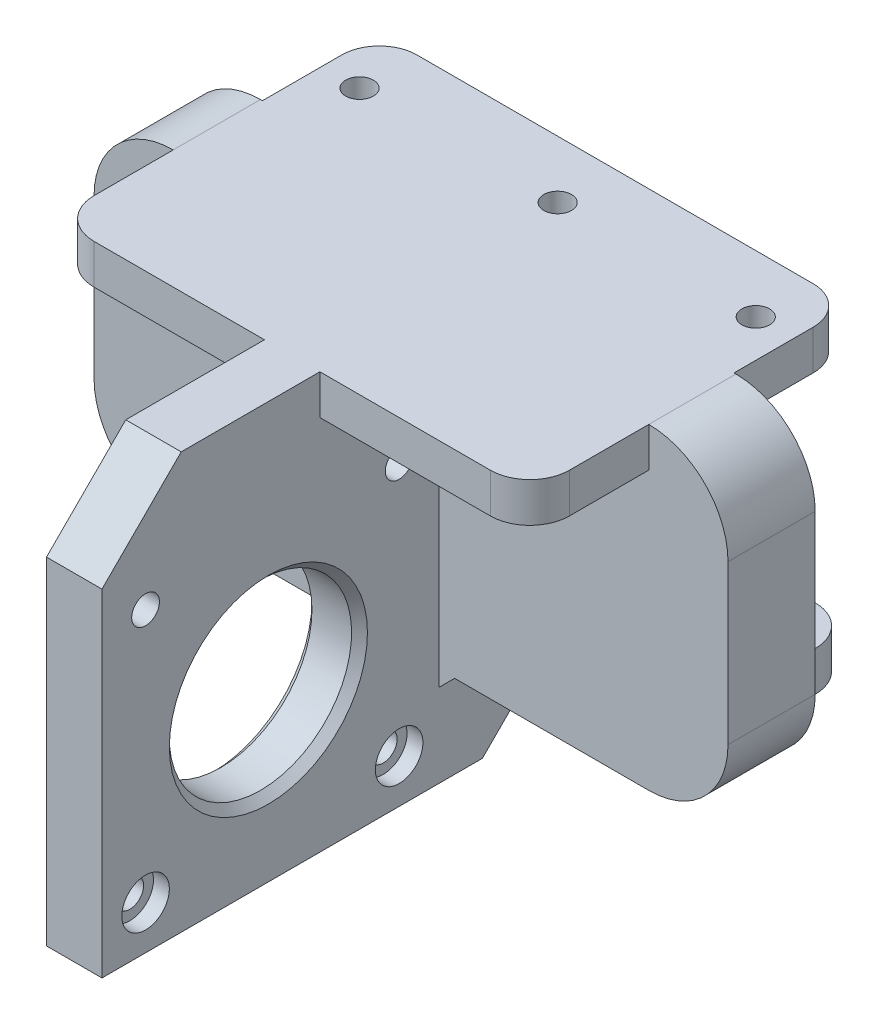
SolidWorks part; units mm, degrees
ref_plane "Front Plane" through (0, 0, 0) normal (0, 0, 1) x (1, 0, 0)
ref_plane "Top Plane" through (0, 0, 0) normal (0, 1, 0) x (1, 0, 0)
ref_plane "Right Plane" through (0, 0, 0) normal (1, 0, 0) x (0, 0, -1)
sketch "Sketch1" plane through (0, 0, 0) normal (0, 0, 1) x (1, 0, 0)
  line L0 (60, 35) -> (0, 35)
  line L1 (0, 35) -> (0, 40)
  line L2 (-10, 30) -> (-10, 10)
  line L3 (0, 0) -> (60, 0)
  line L4 (70, 10) -> (70, 30)
  line L5 (60, 40) -> (60, 35)
  arc A0 (0, 40) -> (-10, 30) centre (0, 30) ccw
  arc A1 (-10, 10) -> (0, 0) centre (0, 10) ccw
  arc A2 (60, 0) -> (70, 10) centre (60, 10) ccw
  arc A3 (70, 30) -> (60, 40) centre (60, 30) ccw
extrude "Boss-Extrude1" add sketch "Sketch1" along normal blind 11
sketch "Sketch2" plane through (0, 0, 11) normal (0, 0, 1) x (1, 0, 0)
  line L1 (0, 35) -> (60, 35)
  line L2 (0, 35) -> (0, 40)
  line L3 (0, 40) -> (60, 40)
  line L4 (60, 35) -> (60, 40)
extrude "Boss-Extrude2" add sketch "Sketch2" against normal blind 26
fillet "Fillet1" radius 5 2 edges at (60, 37.5, -15) (0, 37.5, -15)
sketch "Sketch4" plane through (0, 35, 0) normal (0, -1, 0) x (-1, 0, 0)
  line L0 (-55, 15) -> (-55, 7.5) construction
  line L1 (-30, 15) -> (-30, 7.5) construction
  line L2 (-5, 15) -> (-55, 15) construction
  line L3 (-5, 15) -> (-5, 7.5) construction
  arc A0 (0, 10) -> (-5, 15) centre (-5, 10) ccw construction
  circle A1 centre (-55, 7.5) radius 1.75
  circle A2 centre (-30, 7.5) radius 1.75
  circle A3 centre (-5, 7.5) radius 1.75
  dimension "D2" = 3.5
  dimension "D1" = 7.5
extrude "Cut-Extrude2" cut sketch "Sketch4" against normal blind 25
sketch "Sketch5" plane through (0, 35, 0) normal (0, -1, 0) x (1, 0, 0)
  line L0 (5, -14.75) -> (55, -14.75)
  line L1 (59.75, -10) -> (59.75, -0.25)
  line L3 (0.25, -0.25) -> (0.25, -10)
  line L4 (5, -15) -> (55, -15)
  line L5 (60, -10) -> (60, 0)
  line L6 (60, 0) -> (0, 0)
  line L7 (0, 0) -> (0, -10)
  line L8 (5, -15) -> (55, -15)
  line L9 (60, -10) -> (60, 0)
  line L10 (60, 0) -> (59.75, 0)
  line L11 (0, 0) -> (0, -10)
  line L12 (59.75, -0.25) -> (59.75, 0)
  line L13 (0.25, -0.25) -> (0.25, 0)
  line L14 (0.25, 0) -> (0, 0)
  line L16 (60, 0) -> (0, 0) construction
  line L17 (59.75, -0.25) -> (0.25, -0.25) construction
  arc A0 (55, -14.75) -> (59.75, -10) centre (55, -10) ccw
  arc A1 (0.25, -10) -> (5, -14.75) centre (5, -10) ccw
  arc A2 (55, -15) -> (60, -10) centre (55, -10) ccw
  arc A3 (0, -10) -> (5, -15) centre (5, -10) ccw
  arc A4 (55, -15) -> (60, -10) centre (55, -10) ccw
  arc A5 (0, -10) -> (5, -15) centre (5, -10) ccw
  dimension "D1" = 0
  dimension "D2" = 0.25
extrude "Cut-Extrude3" cut sketch "Sketch5" against normal blind 25
sketch "Sketch6" plane through (0, 0, 11) normal (0, 0, 1) x (1, 0, 0)
  line L1 (60, 40) -> (0, 40)
  line L2 (60, 40) -> (60, 35)
  line L3 (60, 35) -> (0, 35)
  line L4 (0, 40) -> (0, 35)
  dimension "D1" = 5
extrude "Boss-Extrude3" add sketch "Sketch6" along normal blind 15
fillet "Fillet2" radius 5 2 edges at (0, 37.5, 26) (60, 37.5, 26)
sketch "Sketch7" plane through (0, 0, 11) normal (0, 0, 1) x (1, 0, 0)
  line L0 (0, 35) -> (60, 35) construction
  line L1 (33.5, 35) -> (26.5, 35)
  line L2 (33.5, 35) -> (33.5, -10)
  line L3 (33.5, -10) -> (26.5, -10)
  line L4 (26.5, 35) -> (26.5, -10)
  line L5 (0, 0) -> (60, 0) construction
  point P6 (30, -10)
  point P9 (30, 0)
  dimension "D1" = 0
  dimension "D2" = 7
  dimension "D3" = 45
extrude "Boss-Extrude4" add sketch "Sketch7" along normal blind 42.5
ref_plane "Plane1" through (0, 20, 0) normal (0, -1, 0) x (-1, 0, 0)
mirror "Mirror1" about plane through (0, 20, 0) normal (0, -1, 0) of "Cut-Extrude2", "Fillet1", "Boss-Extrude2"
sketch "Sketch8" plane through (26.5, 0, 0) normal (-1, 0, 0) x (0, 0, 1)
  line L0 (53.5, -10) -> (11, -10) construction
  line L2 (11, 35) -> (11, 0) construction
  line L3 (32.5, 8.4983) -> (48, -7.0017) construction
  line L4 (53.5, 35) -> (26, 35) construction
  circle A0 centre (32.5, 8.4983) radius 11.5
  circle A1 centre (48, -7.0017) radius 1.75
  circle A2 centre (16, -7.0017) radius 1.75
  circle A3 centre (16, 24.9983) radius 1.75
  circle A4 centre (48, 24.9983) radius 1.75
  point P3 (32.25, -10)
  point P21 (32, 8.9983)
  dimension "D1" = 23
  dimension "D6" = 3.5
  dimension "D2" = 18.5
  dimension "D3" = 21.5
  dimension "D4" = 45
  dimension "D5" = 15.5
  dimension "D7" = 4
extrude "Cut-Extrude4" cut sketch "Sketch8" against normal blind 42
sketch "Sketch11" plane through (0, -10, 0) normal (0, -1, 0) x (-1, 0, 0)
  line L1 (-26.5, -53.5) -> (-33.5, -53.5)
  line L2 (-26.5, -53.5) -> (-26.5, -11)
  line L3 (-26.5, -11) -> (-33.5, -11)
  line L4 (-33.5, -53.5) -> (-33.5, -11)
extrude "Boss-Extrude6" add sketch "Sketch11" along normal blind 2.5
chamfer "Chamfer8" distance 5 angle 45 1 edges at (30, 35, 53.5)
sketch "Sketch12" plane through (33.5, 0, 0) normal (1, 0, 0) x (0, 0, -1)
  line L0 (-48.5, 35) -> (-26, 35)
  line L1 (-26, 35) -> (-26, 40)
  line L2 (-26, 40) -> (-43.5, 40)
  line L3 (-43.5, 40) -> (-48.5, 35)
  line L4 (-48.5, 35) -> (-53.5, 30) construction
  point P8 (0, 0)
extrude "Boss-Extrude7" add sketch "Sketch12" against normal up to surface (7 mm away) up to face at (26.5, -8.7517, 48)
sketch "Sketch13" plane through (0, 0, 0) normal (0, -1, 0) x (1, 0, 0)
  line L0 (55, -15) -> (5, -15) construction
  line L1 (26.5, 11) -> (33.5, 11)
  line L2 (26.5, 11) -> (26.5, -3.9293)
  line L3 (26.5, -15) -> (33.5, -15)
  line L4 (33.5, 11) -> (33.5, -3.9293)
  line L5 (33.5, -11.0707) -> (33.5, -15)
  line L6 (26.5, -11.0707) -> (26.5, -15)
  circle A0 centre (30, -7.5) radius 1.75
  arc A1 (33.5, -11.0707) -> (33.5, -3.9293) centre (30, -7.5) ccw
  arc A2 (26.5, -3.9293) -> (26.5, -11.0707) centre (30, -7.5) ccw
  dimension "D1" = 5
extrude "Boss-Extrude8" add sketch "Sketch13" along normal blind 5
chamfer "Chamfer9" distance 13 angle 45 1 edges at (30, -5, 11)
chamfer "Chamfer10" distance 3 angle 45 1 edges at (30, -5, -15)
sketch "Sketch14" plane through (0, -5, 0) normal (0, -1, 0) x (-1, 0, 0)
  circle A0 centre (-30, 7.5) radius 3
  dimension "D1" = 6
extrude "Cut-Extrude5" cut sketch "Sketch14" against normal blind 5
chamfer "Chamfer11" distance 2 angle 45 2 edges at (33.5, 0, 3.5354) (26.5, 0, 3.5354)
sketch "Sketch15" plane through (33.5, 0, 0) normal (1, 0, 0) x (0, 0, -1)
  circle A0 centre (-16, -7.0017) radius 3
  circle A1 centre (-48, -7.0017) radius 3
  dimension "D1" = 6
  dimension "D2" = 6
extrude "Cut-Extrude6" cut sketch "Sketch15" against normal blind 2
chamfer "Chamfer12" distance 1 angle 45 2 edges at (26.5, -3.0017, 32.5) (33.5, -3.0017, 32.5)
